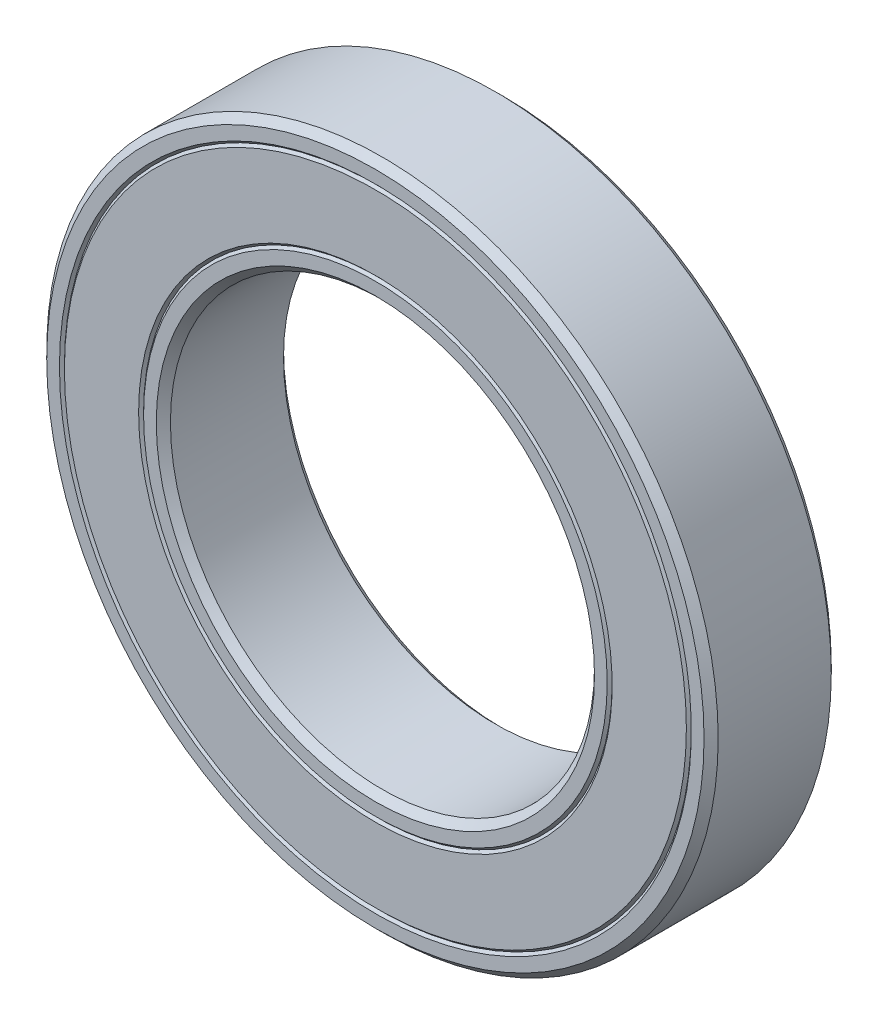
SolidWorks part; units mm, degrees
ref_plane "Front Plane" through (0, 0, 0) normal (0, 0, 1) x (1, 0, 0)
ref_plane "Top Plane" through (0, 0, 0) normal (0, 1, 0) x (1, 0, 0)
ref_plane "Right Plane" through (0, 0, 0) normal (1, 0, 0) x (0, 0, -1)
sketch "Sketch1" plane through (0, 0, 0) normal (0, 0, 1) x (1, 0, 0)
  circle A0 centre (0, 0) radius 47.5
  circle A1 centre (0, 0) radius 30
  dimension "D1" = 95
  dimension "D2" = 60
extrude "Extrude1" add sketch "Sketch1" along normal blind 18
chamfer "Chamfer1" distance 1 angle 45 4 edges at (30, 0, 0) (30, 0, 18) (47.5, 0, 0) (47.5, 0, 18)
sketch "Sketch2" plane through (0, 0, 0) normal (1, 0, 0) x (0, 0, -1)
  line L0 (0, 0) -> (-18, 0) construction
  line L1 (0.2089, 30) -> (-39.5699, 30) construction
  line L2 (-18, 32.8) -> (-17.65, 33.15)
  line L4 (-18, 46.5) -> (-18, -46.5) construction
  line L5 (-17.65, 33.15) -> (-18, 33.5)
  line L6 (-18, 38.75) -> (-13.5691, 38.75) construction
  line L7 (-17.65, 44.35) -> (-18, 44)
  line L8 (-18, 44.7) -> (-17.65, 44.35)
  line L9 (-1, 47.5) -> (-17, 47.5) construction
  line L10 (-18, 32.8) -> (-18, 33.5)
  line L11 (-18, 44.7) -> (-18, 44)
  line L12 (-9, 0) -> (-9, 10.7064) construction
  line L13 (0, 32.8) -> (0, 33.5)
  line L14 (-0.35, 33.15) -> (0, 33.5)
  line L15 (0, 32.8) -> (-0.35, 33.15)
  line L16 (0, 44.7) -> (0, 44)
  line L17 (0, 44.7) -> (-0.35, 44.35)
  line L18 (-0.35, 44.35) -> (0, 44)
  dimension "D1" = 30
  dimension "D2" = 2.8
  dimension "D3" = 0.7
  dimension "D4" = 2.8
revolve "Cut-Revolve1" cut sketch "Sketch2" angle 360 about L0
